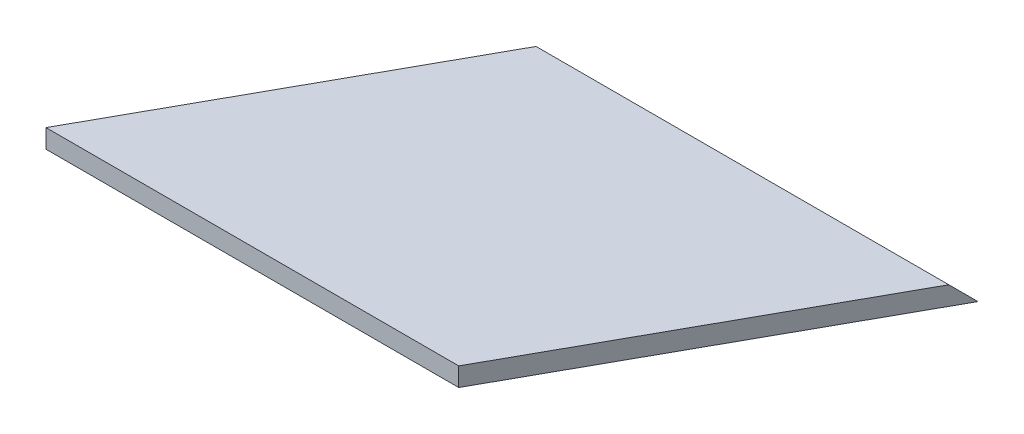
SolidWorks part; units mm, degrees
material "Plain Carbon Steel"
ref_plane "Front Plane" through (0, 0, 0) normal (0, 0, 1) x (1, 0, 0)
ref_plane "Top Plane" through (0, 0, 0) normal (0, 1, 0) x (1, 0, 0)
ref_plane "Right Plane" through (0, 0, 0) normal (1, 0, 0) x (0, 0, -1)
sketch "Sketch1" plane through (0, 0, 0) normal (0, 1, 0) x (1, 0, 0)
  line L0 (-78.0952, -29.7866) -> (-83.0305, -38.6903)
  line L1 (-83.0305, -38.6903) -> (-72.0305, -38.6903)
  line L2 (-72.0305, -38.6903) -> (-67.0952, -29.7866)
  line L3 (-67.0952, -29.7866) -> (-78.0952, -29.7866)
  dimension "D1" = 61
  dimension "D2" = 11
  dimension "D3" = 10.18
extrude "Boss-Extrude1" add sketch "Sketch1" along normal blind 0.5
chamfer "Chamfer1" distance 0.5 angle 45 1 edges at (-72.5952, 0.5, 29.7866)
